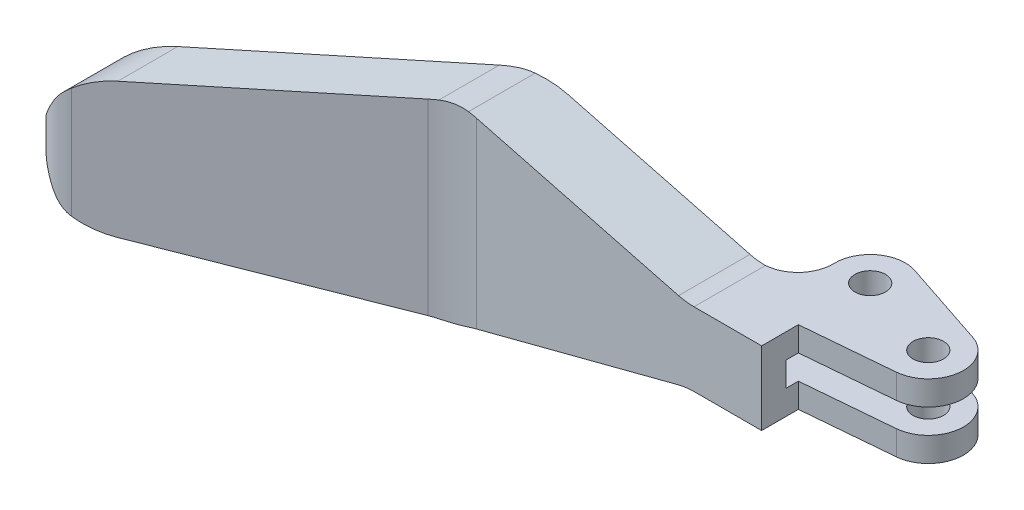
SolidWorks part; units mm, degrees
ref_plane "Front Plane" through (0, 0, 0) normal (0, 0, 1) x (1, 0, 0)
ref_plane "Top Plane" through (0, 0, 0) normal (0, 1, 0) x (1, 0, 0)
ref_plane "Right Plane" through (0, 0, 0) normal (1, 0, 0) x (0, 0, -1)
sketch "Sketch2" plane through (0, 0, 0) normal (0, 1, 0) x (1, 0, 0)
  line L0 (-6.3092, 5.176) -> (0.9216, 2.7718)
  line L1 (0.2546, -2.9099) -> (-7.2308, -3.5648)
  line L2 (-7.2308, -3.5648) -> (-7.2308, -6.6128)
  line L3 (-7.2308, -6.6128) -> (-30.9293, -6.6128)
  line L4 (-34.1043, -7.4635) -> (-52.8681, -18.2968)
  line L5 (-55.6438, -17.553) -> (-55.7708, -17.333)
  line L6 (-55.0271, -14.5573) -> (-32.4596, -1.5279)
  line L7 (-13.0706, -0.6772) -> (-29.2846, -0.6772)
  arc A0 (0.2546, -2.9099) -> (0.9216, 2.7718) centre (0, 0) ccw
  arc A1 (-6.3092, 5.176) -> (-7.2308, 5.3252) centre (-7.2308, 2.4042) ccw
  circle A2 centre (-7.2308, 2.4042) radius 1.27
  circle A3 centre (0, 0) radius 1.27
  arc A4 (-7.2308, 5.3252) -> (-10.1507, 2.324) centre (-7.2308, 2.4042) ccw
  arc A5 (-10.1507, 2.324) -> (-13.0706, -0.6772) centre (-13.0706, 2.2438) cw
  arc A6 (-30.9293, -6.6128) -> (-34.1043, -7.4635) centre (-30.9293, -12.9628) ccw
  arc A7 (-32.4596, -1.5279) -> (-29.2846, -0.6772) centre (-29.2846, -7.0272) cw
  arc A8 (-52.8681, -18.2968) -> (-55.6438, -17.553) centre (-53.8841, -16.537) cw
  arc A9 (-55.7708, -17.333) -> (-55.0271, -14.5573) centre (-54.0111, -16.317) cw
  point P20 (-32.6308, -6.6128)
  point P25 (-54.6278, -19.3128)
  dimension "D1" = 2.54
  dimension "D2" = 2.921
  dimension "D12" = 6.35
  dimension "D13" = 2.032
  dimension "D3" = 7.62
  dimension "D4" = 3.048
  dimension "D5" = 8.89
  dimension "D6" = 5.9356
  dimension "D7" = 25.4
  dimension "D8" = 25.4
  dimension "D9" = 4.318
  dimension "D10" = 150
  dimension "D11" = 95
extrude "Boss-Extrude1" add sketch "Sketch2" along normal blind 16.002
sketch "Sketch3" plane through (0, 0, 6.6128) normal (0, 0, 1) x (1, 0, 0)
  line L0 (-7.2308, 16.002) -> (-7.2308, 0) construction
  line L1 (-7.2308, 6.985) -> (5.4692, 6.985)
  line L2 (-7.2308, 6.985) -> (-7.2308, 9.017)
  line L3 (-7.2308, 9.017) -> (5.4692, 9.017)
  line L4 (5.4692, 6.985) -> (5.4692, 9.017)
  line L5 (-30.9293, 8.001) -> (-7.2308, 8.001) construction
  line L6 (-30.9293, 16.002) -> (-30.9293, 0) construction
  line L7 (2.921, 11.049) -> (-13.5024, 11.049)
  line L8 (2.921, 0) -> (2.921, 16.002) construction
  line L10 (-13.5024, 11.049) -> (-32.5168, 16.002)
  line L11 (-30.9293, 16.002) -> (-34.1043, 16.002) construction
  line L12 (-32.5168, 16.002) -> (-52.8681, 13.3032)
  line L13 (-52.8681, 16.002) -> (-52.8681, 0) construction
  line L14 (-52.8681, 13.3032) -> (-56.0431, 8.001)
  line L15 (-56.0431, 16.002) -> (-56.0431, 0) construction
  line L16 (-56.0431, 8.001) -> (-52.8681, 2.6988)
  line L17 (-52.8681, 2.6988) -> (-32.5168, 0)
  line L18 (-34.1043, 0) -> (-30.9293, 0) construction
  line L19 (-32.5168, 0) -> (-13.5024, 4.953)
  line L20 (-13.5024, 4.953) -> (2.921, 4.953)
  line L21 (2.921, 4.953) -> (2.921, -1.6036)
  line L22 (2.921, -1.6036) -> (-57.5564, -1.6036)
  line L23 (-57.5564, -1.6036) -> (-57.5564, 17.6056)
  line L24 (-57.5564, 17.6056) -> (2.921, 17.6056)
  line L25 (2.921, 17.6056) -> (2.921, 11.049)
  dimension "D1" = 2.032
  dimension "D2" = 12.7
  dimension "D3" = 2.032
extrude "Cut-Extrude1" cut sketch "Sketch3" against normal through all both and the other way through all
fillet "Fillet1" radius 5.08 6 edges at (-13.5024, 4.953, 3.645) (-13.5024, 11.049, 3.645) (-32.5168, 16.002, 4.1877) (-52.8681, 13.3032, 15.8038) (-32.5168, 0, 4.1877) (-52.8681, 2.6988, 15.8038)
sketch "Sketch4" plane through (-7.2308, 0, 0) normal (1, 0, 0) x (0, 0, -1)
  line L0 (5.3252, 9.017) -> (5.3252, 6.985) construction
  line L1 (-4.5808, 6.985) -> (5.3252, 6.985)
  line L2 (-4.5808, 6.985) -> (-4.5808, 9.017)
  line L3 (-4.5808, 9.017) -> (5.3252, 9.017)
  line L4 (5.3252, 6.985) -> (5.3252, 9.017)
  line L5 (1.1342, 9.017) -> (-3.5648, 9.017) construction
  line L6 (1.1342, 6.985) -> (-3.5648, 6.985) construction
  line L7 (-6.6128, 11.049) -> (-6.6128, 4.953) construction
  dimension "D1" = 2.032
extrude "Cut-Extrude2" cut sketch "Sketch4" against normal through all
